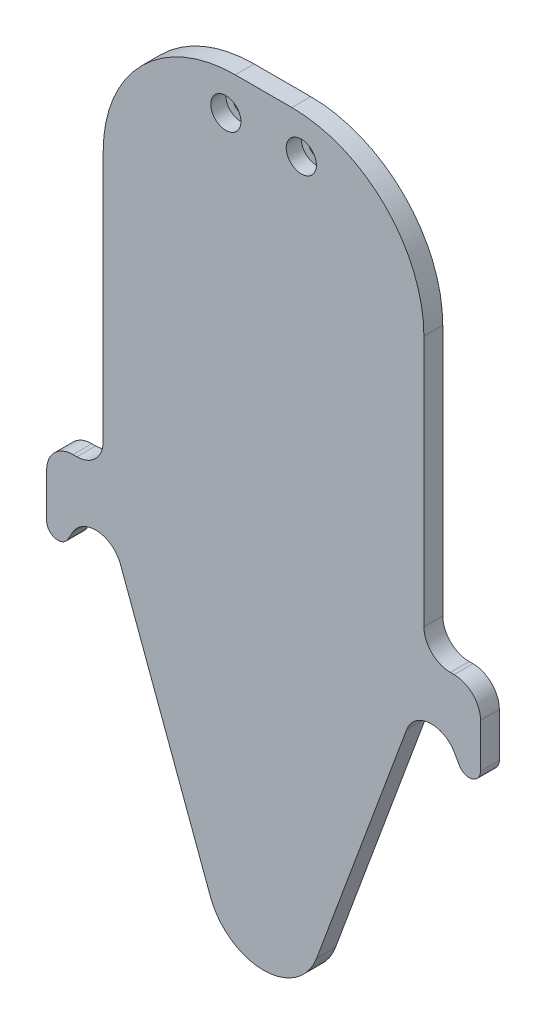
SolidWorks part; units mm, degrees
ref_plane "Płaszczyzna przednia" through (0, 0, 0) normal (0, 0, 1) x (1, 0, 0)
ref_plane "Płaszczyzna górna" through (0, 0, 0) normal (0, 1, 0) x (1, 0, 0)
ref_plane "Płaszczyzna prawa" through (0, 0, 0) normal (1, 0, 0) x (0, 0, -1)
sketch "Szkic1" plane through (0, 0, 0) normal (0, 0, 1) x (1, 0, 0)
  line L0 (-44.5, 0) -> (44.5, 0) construction
  line L1 (0, -61.7621) -> (0, 61.7621) construction
  line L2 (-37.9357, 2.4311) -> (-14.0663, -62.0192)
  line L3 (-11, 54) -> (11, 54) construction
  line L4 (-11, 54) -> (-11, -4) construction
  line L5 (-11, -4) -> (11, -4) construction
  line L6 (11, 54) -> (11, -4) construction
  line L7 (-11, 54) -> (11, -4) construction
  line L8 (-11, -4) -> (11, 54) construction
  line L9 (-27, 76) -> (27, 76) construction
  line L10 (-27, 76) -> (-27, -10) construction
  line L11 (-27, -10) -> (27, -10) construction
  line L12 (27, 76) -> (27, -10) construction
  line L13 (-27, 76) -> (27, -10) construction
  line L14 (-27, -10) -> (27, 76) construction
  line L15 (37.9357, 2.4311) -> (14.0663, -62.0192)
  line L16 (-50.5818, 3.4658) -> (-51.8935, 1.164)
  line L17 (50.5818, 3.4658) -> (51.8935, 1.164)
  line L18 (-57.5, 2.6494) -> (-57.5, 14.3259)
  line L19 (-50.5, 21.3259) -> (-49.5, 21.3259)
  line L20 (-42.5, 28.3259) -> (-42.5, 95)
  line L21 (-7.5, 130) -> (7.5, 130)
  line L22 (42.5, 95) -> (42.5, 28.3259)
  line L23 (49.5, 21.3259) -> (50.5, 21.3259)
  line L24 (57.5, 14.3259) -> (57.5, 2.6494)
  circle A0 centre (-44.5, 0) radius 7 construction
  circle A1 centre (44.5, 0) radius 7 construction
  circle A2 centre (0, 25) radius 22.5 construction
  arc A3 (-14.0663, -62.0192) -> (14.0663, -62.0192) centre (0, -56.8097) ccw
  arc A4 (37.9357, 2.4311) -> (50.5818, 3.4658) centre (44.5, 0) cw
  arc A5 (-50.5818, 3.4658) -> (-37.9357, 2.4311) centre (-44.5, 0) cw
  arc A6 (57.5, 2.6494) -> (51.8935, 1.164) centre (54.5, 2.6494) cw
  arc A7 (-57.5, 2.6494) -> (-51.8935, 1.164) centre (-54.5, 2.6494) ccw
  arc A8 (50.5, 21.3259) -> (57.5, 14.3259) centre (50.5, 14.3259) cw
  arc A9 (42.5, 28.3259) -> (49.5, 21.3259) centre (49.5, 28.3259) ccw
  arc A10 (-57.5, 14.3259) -> (-50.5, 21.3259) centre (-50.5, 14.3259) cw
  arc A11 (-49.5, 21.3259) -> (-42.5, 28.3259) centre (-49.5, 28.3259) ccw
  arc A12 (7.5, 130) -> (42.5, 95) centre (7.5, 95) cw
  arc A13 (-42.5, 95) -> (-7.5, 130) centre (-7.5, 95) cw
  point P8 (0, 25)
  point P14 (0, 33)
  point P18 (0, 0)
  point P27 (0, 130)
  point P30 (55.533, -5.2224)
  point P33 (0, -100)
  point P34 (0, 0)
  point P37 (-55.533, -5.2224)
  point P43 (57.5, -8.6741)
  point P46 (-57.5, -8.6741)
  point P49 (57.5, 21.3259)
  point P52 (42.5, 21.3259)
  point P55 (-57.5, 21.3259)
  point P58 (-42.5, 21.3259)
  dimension "D2" = 14
  dimension "D3" = 14
  dimension "D4" = 22
  dimension "D7" = 45
  dimension "D12" = 15
  dimension "D18" = 3
  dimension "D19" = 30
  dimension "D24" = 7
  dimension "D25" = 35
  dimension "D1" = 89
  dimension "D5" = 58
  dimension "D6" = 4
  dimension "D8" = 54
  dimension "D9" = 86
  dimension "D10" = 35
  dimension "D11" = 100
  dimension "D13" = 10
  dimension "D14" = 10
  dimension "D15" = 50
  dimension "D16" = 50
  dimension "D17" = 30
  dimension "D20" = 15
  dimension "D21" = 15
  dimension "D22" = 130
  dimension "D23" = 85
extrude "Dodanie-wyciągnięcie1" add sketch "Szkic1" along normal blind 5 contours A12 L22 A9 L23 A8 L24 A6 L17 A4 L15 A3 L2 A5 L16 A7 L18 A10 L19 A11 L20 A13 L21
sketch "Szkic2" plane through (0, 0, 0) normal (0, 0, -1) x (-1, 0, 0)
  line L1 (-27, 78) -> (27, 78)
  line L2 (-30, 75) -> (-30, -9)
  line L3 (-27, -12) -> (27, -12)
  line L4 (30, 75) -> (30, -9)
  line L5 (-30, 78) -> (30, -12) construction
  line L6 (-30, -12) -> (30, 78) construction
  arc A0 (-30, -9) -> (-27, -12) centre (-27, -9) ccw
  arc A1 (27, -12) -> (30, -9) centre (27, -9) ccw
  arc A2 (27, 78) -> (30, 75) centre (27, 75) cw
  arc A3 (-27, 78) -> (-30, 75) centre (-27, 75) ccw
  point P0 (0, 33)
  dimension "D3" = 3
  dimension "D1" = 60
  dimension "D2" = 90
extrude "Wytnij-wyciągnięcie1" cut sketch "Szkic2" against normal blind 1
sketch "Szkic3" plane through (0, 0, 0) normal (0, 0, -1) x (-1, 0, 0)
  line L0 (-61.395, 120) -> (61.395, 120) construction
  line L1 (7.5, 130) -> (-7.5, 130) construction
  circle A0 centre (-10, 120) radius 2
  circle A1 centre (10, 120) radius 2
  point P2 (0, 120)
  point P5 (0, 130)
  dimension "D2" = 4
  dimension "D3" = 4
  dimension "D1" = 10
  dimension "D4" = 10
  dimension "D5" = 10
extrude "Wytnij-wyciągnięcie2" cut sketch "Szkic3" against normal up to surface (5 mm away) up to face at (0, 23.8381, 5)
sketch "Szkic4" plane through (0, 0, 5) normal (0, 0, 1) x (1, 0, 0)
  circle A0 centre (-10, 120) radius 4
  circle A1 centre (10, 120) radius 4
  dimension "D1" = 8
  dimension "D2" = 8
extrude "Wytnij-wyciągnięcie3" cut sketch "Szkic4" against normal blind 4
sketch "Szkic5" plane through (0, 0, 0) normal (0, 0, -1) x (-1, 0, 0)
  circle A0 centre (-10, 120) radius 2
  circle A1 centre (10, 120) radius 2
  circle A2 centre (-10, 120) radius 5
  circle A3 centre (10, 120) radius 5
  dimension "D1" = 10
  dimension "D2" = 10
extrude "Dodanie-wyciągnięcie2" add sketch "Szkic5" along normal blind 5
fillet "Zaokrąglenie1" radius 2 4 edges at (5, 120, 0) (-15, 120, 0) (-15, 120, -5) (5, 120, -5)
